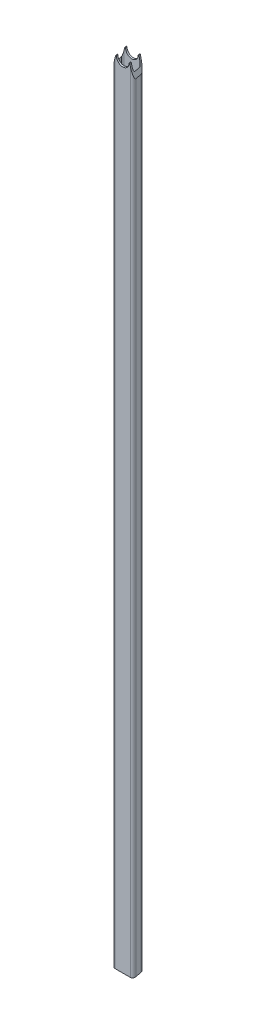
SolidWorks part; units mm, degrees
note: '?' marks a value the reader was unsure of.
other "Исправление1"
sketch "Эскиз2" plane through (15, 2000, 10) normal (0.5774, 0.5773, 0.5774) x (0.7071, 0, -0.7071)
material "Ст 3 ГОСТ 380-88"
ref_plane "Спереди" through (0, 0, 0) normal (0, 0, 1) x (1, 0, 0)
ref_plane "Сверху" through (0, 0, 0) normal (0, 1, 0) x (1, 0, 0)
ref_plane "Справа" through (0, 0, 0) normal (1, 0, 0) x (0, 0, -1)
ref_plane "Плоскость1" through (0, 1130, 0) normal (0, 1, 0) x (1, 0, 0)
ref_plane "Плоскость2" through (0, 0, -7.5) normal (0, 0, 1) x (1, 0, 0)
sketch "Эскиз1" plane through (0, 0, 0) normal (0, 1, 0) x (1, 0, 0)
  line L0 (-15, 7.5) -> (15, -7.5) construction
  line L1 (-11, 7.5) -> (11, 7.5)
  line L2 (-15, 3.5) -> (-15, -3.5)
  line L3 (-11, -7.5) -> (11, -7.5)
  line L4 (15, 3.5) -> (15, -3.5)
  line L5 (-15, -7.5) -> (15, 7.5) construction
  arc A0 (-15, -3.5) -> (-11, -7.5) centre (-11, -3.5) ccw
  arc A1 (11, -7.5) -> (15, -3.5) centre (11, -3.5) ccw
  arc A2 (11, 7.5) -> (15, 3.5) centre (11, 3.5) cw
  arc A3 (-11, 7.5) -> (-15, 3.5) centre (-11, 3.5) ccw
  point P4 (0, 0)
  dimension "D3" = 4
  dimension "D1" = 30
  dimension "D2" = 15
extrude "Вытянуть-Тонкостенный1" add sketch "Эскиз1" along normal up to surface (1130 mm away) thin up to plane "Плоскость1" thin type one direction reverse wall 2
ref_axis "Ось2" through (80.9, 1130, -7.5) along (-1, 0, 0)?
ref_plane "Плоскость4" through (0, 1052.4294, 281.9976) normal (0, 0.9659, 0.2588) x (-1, 0, 0)
ref_plane "Плоскость5" through (0, 77.5706, -289.4976) normal (0, 0.2588, -0.9659) x (-1, 0, 0)
other "Сечение2" flip cut yes
ref_axis "Ось3" through (0, 50, -296.8851) along (0, 0.9659, 0.2588)?
ref_point "Точка1"
sketch "Эскиз4" plane through (0, 77.5706, -289.4976) normal (0, 0.2588, -0.9659) x (-1, 0, 0)
  line L0 (-9, 1089.555) -> (-10, 1089.555)
  line L1 (-10, 1089.555) -> (-20, 1052.2345)
  line L2 (-20, 1052.2345) -> (-20, 1094.555)
  line L3 (-20, 1094.555) -> (20, 1094.555)
  line L4 (20, 1094.555) -> (20, 1052.2345)
  line L5 (20, 1052.2345) -> (10, 1089.555)
  line L6 (10, 1089.555) -> (9, 1089.555)
  circle A0 centre (0, 1089.555) radius 9 construction
  arc A1 (-9, 1089.555) -> (9, 1089.555) centre (0, 1089.555) ccw
  point P3 (-9, 1089.555)
  point P4 (9, 1089.555)
  dimension "D1" = 18
  dimension "D2" = 1
  dimension "D3" = 1
  dimension "D4" = 105
  dimension "D5" = 105
  dimension "D6" = 20
  dimension "D7" = 20
  dimension "D8" = 5
extrude "Вырез-Вытянуть1" cut sketch "Эскиз4" against normal blind 40
ref_plane "Плоскость6" through (0, 0, 7.5) normal (0, 0, 1) x (1, 0, 0)
ref_axis "Ось4" through (-80.9, 0, 7.5) along (1, 0, 0)?
ref_plane "Плоскость7" through (0, 1.875, 0.5024) normal (0, 0.9659, 0.2588) x (1, 0, 0)
other "Сечение3"
